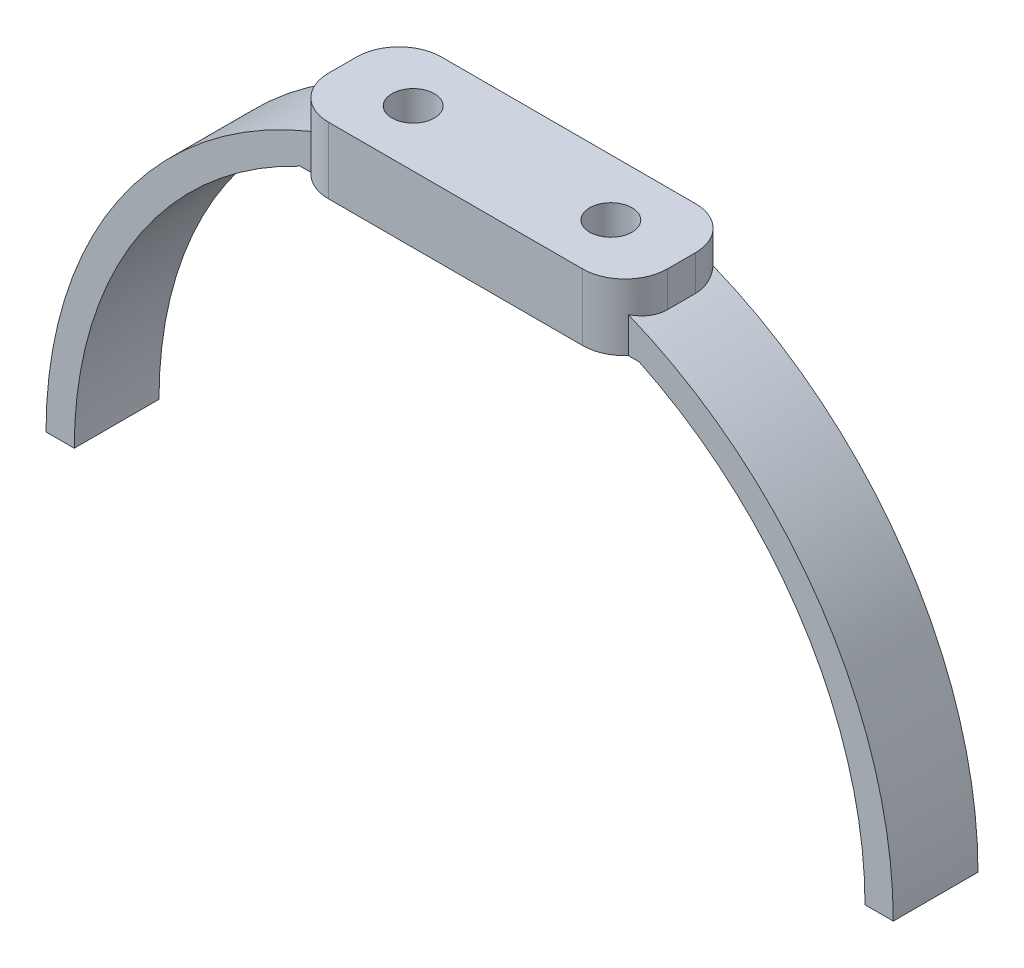
SolidWorks part; units mm, degrees
ref_plane "前视基准面" through (0, 0, 0) normal (0, 0, 1) x (1, 0, 0)
ref_plane "上视基准面" through (0, 0, 0) normal (0, 1, 0) x (1, 0, 0)
ref_plane "右视基准面" through (0, 0, 0) normal (1, 0, 0) x (0, 0, -1)
sketch "草图2" plane through (0, 0, 0) normal (0, 1, 0) x (1, 0, 0)
  line L1 (12, 4) -> (-12, 4)
  line L2 (12, 4) -> (12, -4)
  line L3 (12, -4) -> (-12, -4)
  line L4 (-12, 4) -> (-12, -4)
  line L5 (12, 4) -> (-12, -4) construction
  line L6 (12, -4) -> (-12, 4) construction
  point P0 (0, 0)
extrude "凸台-拉伸1" add sketch "草图2" against normal blind 1
sketch "草图5" plane through (0, 0, 0) normal (0, 0, 1) x (1, 0, 0)
  line L0 (0, 0) -> (0, -30) construction
  line L1 (-30, -30) -> (-28, -30)
  line L2 (30, -30) -> (28, -30)
  arc A0 (0, 0) -> (-30, -30) centre (0, -30) ccw
  arc A1 (0, 0) -> (30, -30) centre (0, -30) cw
  arc A2 (28, -30) -> (-28, -30) centre (0, -30) ccw
  dimension "D1" = 30
  dimension "D2" = 2
extrude "凸台-拉伸3" add sketch "草图5" along normal blind 3 and the other way blind 3 separate body contours A1 L0 A2 L2 | L0 A0 L1 A2 | L1 A0 A1 L2 A2 region at (20.9132, -9.0868, 0) region at (-0.4243, -1, 0)
sketch "草图7" plane through (0, 0, 4) normal (0, 0, 1) x (1, 0, 0)
  line L0 (-12, 0) -> (12, 0) construction
  line L1 (-12, 0) -> (12, 0) construction
  line L3 (-12, 0) -> (12, 0)
  line L4 (-12, 0) -> (-12, -4.7018)
  line L5 (-12, -4.7018) -> (12, -4.7018)
  line L6 (12, 0) -> (12, -4.7018)
  arc A0 (28, -30) -> (-28, -30) centre (0, -30) ccw construction
  arc A1 (28, -30) -> (-28, -30) centre (0, -30) ccw construction
extrude "凸台-拉伸5" add sketch "草图7" against normal up to surface (8 mm away) up to face at (0, -0.5, -4)
sketch "草图3" plane through (0, 0, 0) normal (0, 1, 0) x (1, 0, 0)
  circle A0 centre (0, 0) radius 7 construction
  circle A1 centre (-7, 0) radius 1.5
  circle A2 centre (7, 0) radius 1.5
extrude "切除-拉伸1" cut sketch "草图3" against normal through all
fillet "圆角1" radius 3 4 edges at (-12, -2.3509, 4) (-12, -2.3509, -4) (12, -2.3509, 4) (12, -2.3509, -4)
